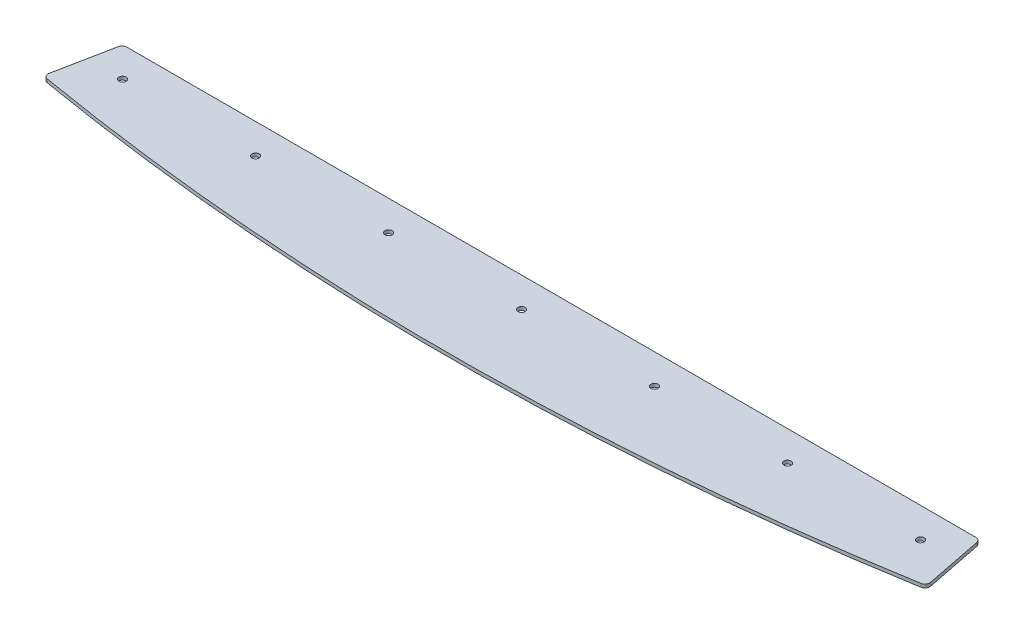
SolidWorks part; units mm, degrees
ref_plane "Front Plane" through (0, 0, 0) normal (0, 0, 1) x (1, 0, 0)
ref_plane "Top Plane" through (0, 0, 0) normal (0, 1, 0) x (1, 0, 0)
ref_plane "Right Plane" through (0, 0, 0) normal (1, 0, 0) x (0, 0, -1)
sketch "Sketch1" plane through (0, 0, 0) normal (0, 1, 0) x (1, 0, 0)
  line L0 (0, 0) -> (0, -2150) construction
  line L1 (0, 0) -> (-419.4442, -2108.6884) construction
  line L2 (0, 0) -> (419.4442, -2108.6884) construction
  line L4 (-394.8962, -2088.4231) -> (394.8962, -2088.4231) construction
  line L9 (24.5196, -4.8773) -> (-394.9246, -2113.5656) construction
  line L10 (-24.5196, -4.8773) -> (394.9246, -2113.5656) construction
  line L11 (0, -2088.4231) -> (110, -2088.4231) construction
  line L12 (0, -2088.4231) -> (-110, -2088.4231) construction
  line L13 (-354.4236, -2063.7282) -> (-365.3637, -2118.7282)
  line L14 (-354.4236, -2063.7282) -> (354.4236, -2063.7282)
  line L15 (354.4236, -2063.7282) -> (365.3637, -2118.7282)
  circle A1 centre (0, 0) radius 2150 construction
  circle A4 centre (0, -2088.4231) radius 3
  circle A5 centre (110, -2088.4231) radius 3
  circle A6 centre (220, -2088.4231) radius 3
  circle A7 centre (330, -2088.4231) radius 3
  circle A8 centre (-110, -2088.4231) radius 3
  circle A9 centre (-220, -2088.4231) radius 3
  circle A10 centre (-330, -2088.4231) radius 3
  arc A13 (-365.3637, -2118.7282) -> (365.3637, -2118.7282) centre (0, 0) ccw
  dimension "D3" = 4300
  dimension "D10" = 6
  dimension "D15" = 55
  dimension "D4" = 55
  dimension "D1" = 2150
  dimension "D2" = 22.5
  dimension "D5" = 25
  dimension "D6" = 25
  dimension "D12" = 110
  dimension "D14" = 110
  dimension "D11" = 4
  dimension "D13" = 4
extrude "Boss-Extrude1" add sketch "Sketch1" along normal blind 2.8
ref_axis "Axis1" through (0, 6.3, 0) along (0, -1, 0)
fillet "Fillet1" radius 4 4 edges at (-365.3637, 1.4, 2118.7282) (-354.4236, 1.4, 2063.7282) (354.4236, 1.4, 2063.7282) (365.3637, 1.4, 2118.7282)
